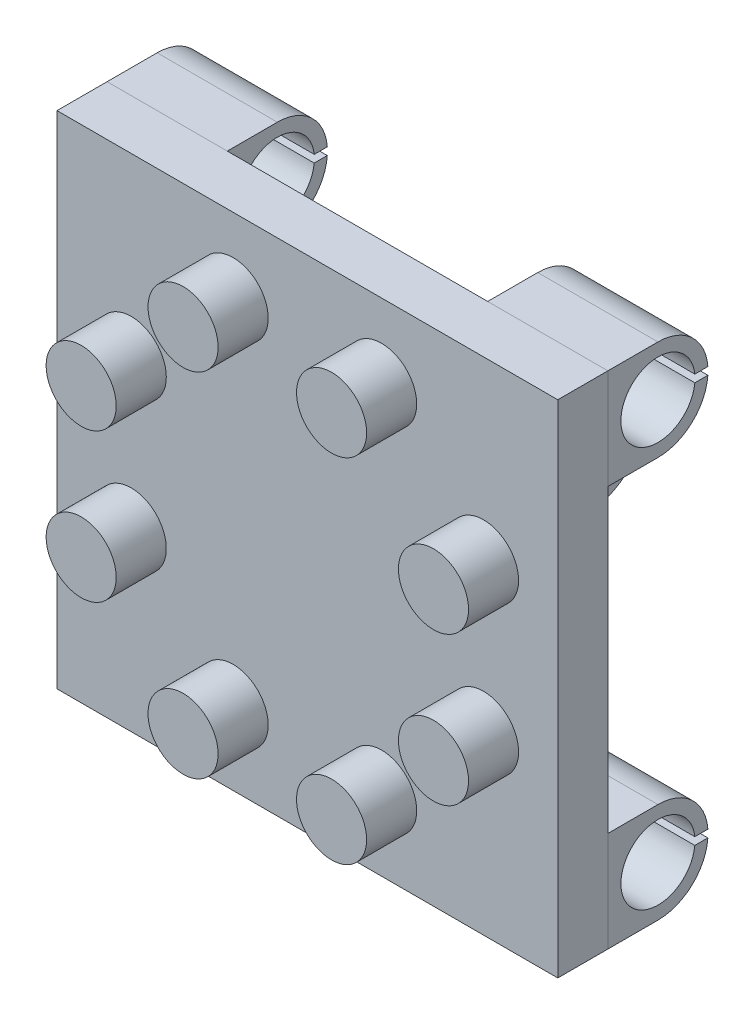
SolidWorks part; units mm, degrees
ref_plane "Plano frontal" through (0, 0, 0) normal (0, 0, 1) x (1, 0, 0)
ref_plane "Plano superior" through (0, 0, 0) normal (0, 1, 0) x (1, 0, 0)
ref_plane "Plano direito" through (0, 0, 0) normal (1, 0, 0) x (0, 0, -1)
sketch "Esboço1" plane through (0, 0, 0) normal (0, 0, 1) x (1, 0, 0)
  line L1 (-25.8743, 34.174) -> (-25.8743, -39.4705) construction
  line L2 (-25.8743, 21.9595) -> (37.4155, 21.9595) construction
  line L3 (24.1257, -28.0405) -> (24.1257, 21.9595) construction
  line L4 (-25.8743, 21.9595) -> (-11.0487, 7.134) construction
  line L5 (-11.0487, 7.134) -> (9.3002, -13.2149) construction
  line L6 (9.3002, -13.2149) -> (24.1257, -28.0405) construction
  line L7 (-25.8743, -28.0405) -> (24.1257, 21.9595) construction
  line L9 (-25.8743, 21.9595) -> (24.1257, 21.9595)
  line L10 (-25.8743, 21.9595) -> (-25.8743, -28.0405)
  line L11 (-25.8743, -28.0405) -> (24.1257, -28.0405)
  line L12 (24.1257, 21.9595) -> (24.1257, -28.0405)
  dimension "D1" = 50
extrude "Ressalto-extrusão1" add sketch "Esboço1" along normal blind 10
sketch "Esboço2" plane through (0, 0, 10) normal (0, 0, 1) x (1, 0, 0)
  line L0 (-25.8743, -28.0405) -> (27.247, -28.0405) construction
  line L1 (-11.0487, 21.9595) -> (-11.0487, -28.0405) construction
  line L2 (24.1257, 21.9595) -> (-25.8743, 21.9595) construction
  line L3 (9.3002, 21.9595) -> (9.3002, -28.0405) construction
  line L4 (-25.8743, -28.0405) -> (-25.8743, 21.9595) construction
  line L5 (-25.8743, 7.134) -> (24.1257, 7.134) construction
  line L6 (24.1257, -28.0405) -> (24.1257, 21.9595) construction
  line L7 (-25.8743, -13.2149) -> (24.1257, -13.2149) construction
  circle A0 centre (-11.0487, 7.134) radius 7
  circle A3 centre (9.3002, -13.2149) radius 7
extrude "Ressalto-extrusão2" add sketch "Esboço2" along normal blind 10
mirror "Espelhar11" about plane through (-25.8743, 21.9595, 10) normal (1, 0, 0) of "Ressalto-extrusão2", "Ressalto-extrusão1"
mirror "Espelhar12" about plane through (-25.8743, -28.0405, 10) normal (0, 1, 0) of "Ressalto-extrusão2", "Ressalto-extrusão1"
mirror "Espelhar13" about plane through (-25.8743, -78.0405, 10) normal (-1, 0, 0) of "Espelhar12"
sketch "Esboço3" plane through (0, 0, 0) normal (0, 0, -1) x (-1, 0, 0)
  line L2 (-24.1257, -78.0405) -> (-0.1257, -78.0405)
  line L5 (-24.1257, -78.0405) -> (-24.1257, -58.0405)
  line L31 (-24.1257, -58.0405) -> (-0.1257, -58.0405)
  line L35 (-0.1257, -78.0405) -> (-0.1257, -58.0405)
  line L41 (51.8743, -78.0405) -> (75.8743, -78.0405)
  line L54 (51.8743, -78.0405) -> (51.8743, -58.0405)
  line L55 (51.8743, -58.0405) -> (75.8743, -58.0405)
  line L56 (75.8743, -78.0405) -> (75.8743, -58.0405)
  line L57 (51.8743, 1.9595) -> (75.8743, 1.9595)
  line L58 (51.8743, 1.9595) -> (51.8743, 21.9595)
  line L59 (51.8743, 21.9595) -> (75.8743, 21.9595)
  line L60 (75.8743, 1.9595) -> (75.8743, 21.9595)
  line L61 (-24.1257, 1.9595) -> (-0.1257, 1.9595)
  line L62 (-24.1257, 1.9595) -> (-24.1257, 21.9595)
  line L63 (-24.1257, 21.9595) -> (-0.1257, 21.9595)
  line L64 (-0.1257, 1.9595) -> (-0.1257, 21.9595)
  dimension "D1" = 24
  dimension "D2" = 20
extrude "Ressalto-extrusão3" add sketch "Esboço3" along normal blind 20 separate body
fillet "Filete3" radius 10 2 edges at (12.1257, -58.0405, -20) (12.1257, -78.0405, -20)
fillet "Filete4" radius 10 2 edges at (-63.8743, -58.0405, -20) (-63.8743, -78.0405, -20)
fillet "Filete5" radius 10 2 edges at (12.1257, 21.9595, -20) (12.1257, 1.9595, -20)
fillet "Filete6" radius 10 2 edges at (-63.8743, 21.9595, -20) (-63.8743, 1.9595, -20)
sketch "Esboço4" plane through (24.1257, 0, 0) normal (1, 0, 0) x (0, 0, -1)
  line L0 (20, -68.0405) -> (17.4, -68.0405) construction
  line L1 (0, -58.0405) -> (0, -78.0405) construction
  line L2 (10, -78.0405) -> (10, -58.0405) construction
  line L3 (10, 1.9595) -> (10, 21.9595) construction
  line L4 (20, 11.9595) -> (0, 11.9595) construction
  line L5 (0, 21.9595) -> (0, 1.9595) construction
  line L6 (16.8497, -68.0405) -> (0, -68.0405) construction
  line L11 (20.3514, -68.7905) -> (17.3619, -68.7905)
  line L12 (20.3514, -68.7905) -> (20.3514, -67.2905)
  line L13 (20.3514, -67.2905) -> (17.3619, -67.2905)
  line L15 (20.3514, 11.2095) -> (17.3619, 11.2095)
  line L16 (20.3514, 11.2095) -> (20.3514, 12.7095)
  line L17 (20.3514, 12.7095) -> (17.3619, 12.7095)
  arc A0 (17.3619, -67.2905) -> (17.3619, -68.7905) centre (10, -68.0405) ccw
  arc A2 (17.3619, 12.7095) -> (17.3619, 11.2095) centre (10, 11.9595) ccw
  point P25 (10, 11.9595)
  dimension "D1" = 14.8
  dimension "D2" = 1.5
extrude "Corte-extrusão1" cut sketch "Esboço4" against normal through all both and the other way through all
sketch "Esboço5" plane through (0, 0, 0) normal (0, 0, -1) x (-1, 0, 0)
  line L0 (75.8743, -28.0405) -> (-24.1257, -28.0405) construction
  line L1 (75.8743, -78.0405) -> (75.8743, 21.9595) construction
  line L2 (-24.1257, -78.0405) -> (-24.1257, 21.9595) construction
  line L3 (25.8743, -78.0405) -> (25.8743, 21.9595) construction
  line L4 (-24.1257, -78.0405) -> (75.8743, -78.0405) construction
  line L5 (-24.1257, 21.9595) -> (75.8743, 21.9595) construction
  line L6 (43.3743, -28.0405) -> (8.3743, -28.0405) construction
  line L7 (43.3743, -43.0405) -> (8.3743, -43.0405)
  line L8 (43.3743, -43.0405) -> (43.3743, -13.0405)
  line L9 (43.3743, -13.0405) -> (8.3743, -13.0405)
  line L10 (8.3743, -43.0405) -> (8.3743, -13.0405)
  line L11 (25.8743, -43.0405) -> (25.8743, -13.0405) construction
  point P20 (25.8743, -28.0405)
  point P21 (25.8743, -28.0405)
  dimension "D1" = 35
  dimension "D2" = 30
extrude "Ressalto-extrusão4" add sketch "Esboço5" along normal blind 50
sketch "Esboço6" plane through (-43.3743, 0, 0) normal (-1, 0, 0) x (0, 0, 1)
  line L0 (-50, -28.0405) -> (0, -28.0405) construction
  line L1 (-50, -43.0405) -> (-50, -13.0405) construction
  line L2 (0, -78.0405) -> (0, 21.9595) construction
  line L3 (-25, -43.0405) -> (-25, -13.0405) construction
  line L4 (-50, -43.0405) -> (0, -43.0405) construction
  line L5 (-50, -13.0405) -> (0, -13.0405) construction
  line L6 (-25, -43.0405) -> (-50, -13.0405) construction
  line L7 (-25, -13.0405) -> (-50, -43.0405) construction
  circle A0 centre (-37.5, -28.0405) radius 11.5
  dimension "D1" = 23
sketch "Esboço7" plane through (0, -43.0405, 0) normal (0, -1, 0) x (1, 0, 0)
  line L0 (-25.8743, -50) -> (-25.8743, 0) construction
  line L1 (-8.3743, -50) -> (-43.3743, -50) construction
  line L2 (-8.3743, 0) -> (-43.3743, 0) construction
  line L3 (-25.8743, -50) -> (-32.8743, -50) construction
  line L4 (-25.8743, -50) -> (-18.8743, -50) construction
  line L5 (-8.3743, 0) -> (-8.3743, -50)
  line L6 (-18.8743, -50) -> (-8.3743, -50)
  line L7 (-43.3743, 0) -> (-43.3743, -50)
  line L8 (-32.8743, -50) -> (-43.3743, -50)
  arc A0 (-32.8743, -50) -> (-43.3743, 0) centre (-157.1719, -50) ccw
  arc A1 (-18.8743, -50) -> (-8.3743, 0) centre (105.4234, -50) cw
extrude "Corte-extrusão2" cut sketch "Esboço7" against normal through all both and the other way through all
extrude "Corte-extrusão3" cut sketch "Esboço6" against normal blind 15
sketch "Esboço8" plane through (-28.3743, 0, 0) normal (-1, 0, 0) x (0, 0, 1)
  circle A0 centre (-37.5, -28.0405) radius 5.25
  circle A1 centre (-37.5, -28.0405) radius 11.5 construction
  dimension "D1" = 10.5
extrude "Corte-extrusão4" cut sketch "Esboço8" against normal through all
fillet "Filete7" radius 10 2 edges at (-25.8743, -13.0405, -50) (-25.8743, -43.0405, -50)
